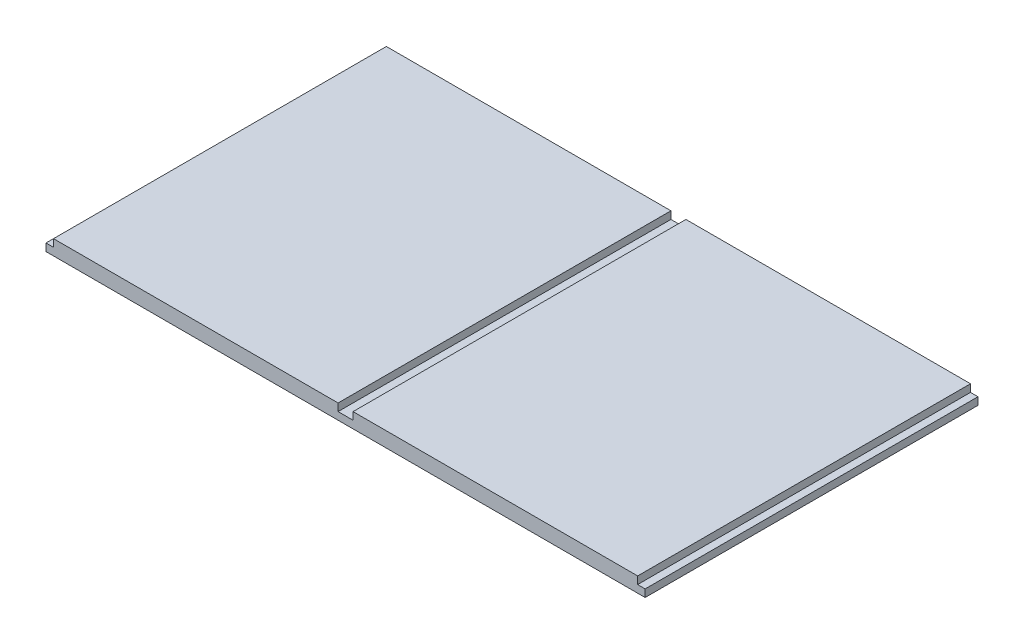
SolidWorks part; units mm, degrees
ref_plane "Front" through (0, 0, 0) normal (0, 0, 1) x (1, 0, 0)
ref_plane "Top" through (0, 0, 0) normal (0, 1, 0) x (1, 0, 0)
ref_plane "Right" through (0, 0, 0) normal (1, 0, 0) x (0, 0, -1)
sketch "Sketch1" plane through (0, 0, 0) normal (0, 1, 0) x (1, 0, 0)
  line L1 (-360, -200) -> (360, -200)
  line L2 (-360, -200) -> (-360, 200)
  line L3 (-360, 200) -> (360, 200)
  line L4 (360, -200) -> (360, 200)
  line L5 (-360, -200) -> (360, 200) construction
  line L6 (-360, 200) -> (360, -200) construction
  point P0 (0, 0)
  dimension "D1" = 720
  dimension "D2" = 400
extrude "Boss-Extrude1" add sketch "Sketch1" along normal blind 18
sketch "Sketch2" plane through (0, 18, 0) normal (0, 1, 0) x (1, 0, 0)
  line L0 (360, 200) -> (-360, 200) construction
  line L1 (360, -200) -> (351, -200)
  line L2 (360, -200) -> (360, 200)
  line L3 (360, 200) -> (351, 200)
  line L4 (351, -200) -> (351, 200)
  line L6 (-360, -200) -> (-351, -200)
  line L7 (-360, -200) -> (-360, 200)
  line L8 (-360, 200) -> (-351, 200)
  line L9 (-351, -200) -> (-351, 200)
  dimension "D1" = 9
  dimension "D2" = 9
extrude "Cut-Extrude1" cut sketch "Sketch2" against normal blind 9
sketch "Sketch3" plane through (0, 18, 0) normal (0, 1, 0) x (1, 0, 0)
  line L0 (351, 200) -> (-351, 200) construction
  line L1 (-9, -200) -> (9, -200)
  line L2 (-9, -200) -> (-9, 200)
  line L3 (-9, 200) -> (9, 200)
  line L4 (9, -200) -> (9, 200)
  line L5 (-9, -200) -> (9, 200) construction
  line L6 (-9, 200) -> (9, -200) construction
  point P0 (0, 0)
  dimension "D1" = 18
extrude "Cut-Extrude2" cut sketch "Sketch3" against normal blind 9
